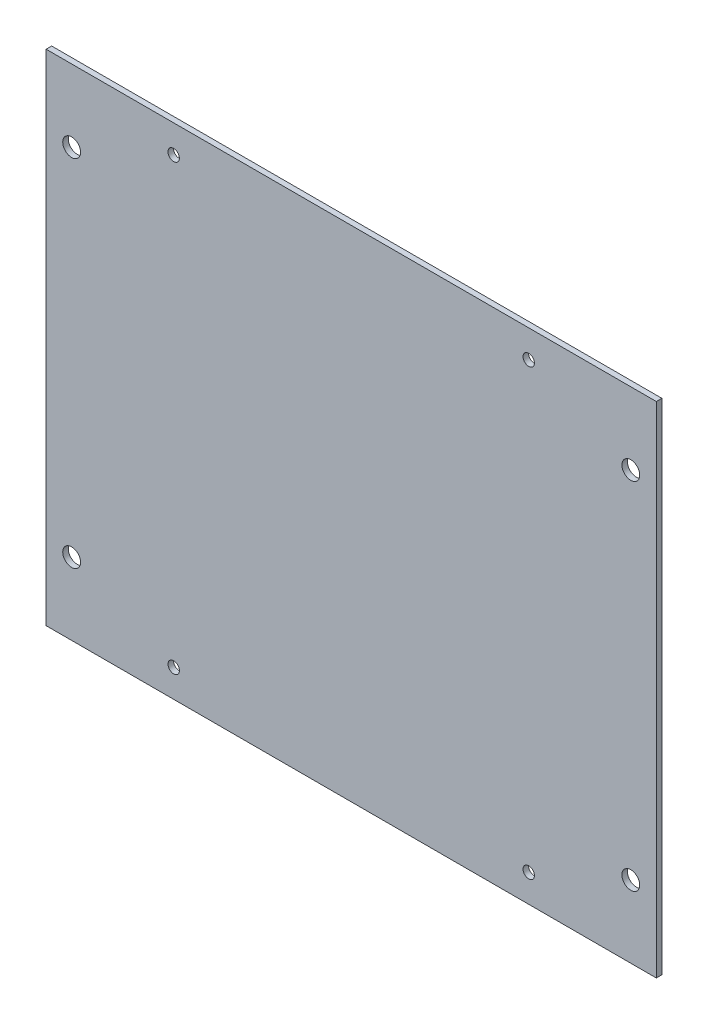
SolidWorks part; units mm, degrees
material "Perspex (TM) GS Acrylic Cast Sheet"
ref_plane "Front Plane" through (0, 0, 0) normal (0, 0, 1) x (1, 0, 0)
ref_plane "Top Plane" through (0, 0, 0) normal (0, 1, 0) x (1, 0, 0)
ref_plane "Right Plane" through (0, 0, 0) normal (1, 0, 0) x (0, 0, -1)
sketch "Sketch1" plane through (0, 0, 0) normal (0, 0, 1) x (1, 0, 0)
  line L1 (-457.2, -304.8) -> (457.2, -304.8)
  line L2 (-457.2, -304.8) -> (-457.2, 304.8)
  line L3 (-457.2, 304.8) -> (457.2, 304.8)
  line L4 (457.2, -304.8) -> (457.2, 304.8)
  line L5 (0, 304.8) -> (0, -304.8) construction
  line L6 (-457.2, 0) -> (457.2, 0) construction
  point P0 (0, 0)
  point P4 (-320.04, 0)
  point P5 (320.04, 0)
  point P6 (0, 213.36)
  point P7 (0, -213.36)
  dimension "Length" = 914.4
  dimension "Width" = 609.6
  dimension "Break" = 137.16
  dimension "D2" = 137.16
  dimension "D1" = 91.44
  dimension "D3" = 91.44
sketch "Sketch2" plane through (0, 0, 0) normal (1, 0, 0) x (0, 0, -1)
  line L0 (-0.7938, -304.8) -> (0.7938, -304.8)
  dimension "Thickness" = 1.5875
sketch "Sketch3" plane through (0, 0, 0) normal (0, 0, 1) x (1, 0, 0)
  line L0 (-457.2, -304.8) -> (-457.2, 304.8) construction
  line L1 (-457.2, -304.8) -> (457.2, -304.8) construction
  line L2 (457.2, -304.8) -> (457.2, 304.8) construction
  line L3 (-457.2, 304.8) -> (457.2, 304.8) construction
  line L4 (-457.2, -304.8) -> (-457.2, 304.8)
  line L5 (-457.2, -304.8) -> (457.2, -304.8)
  line L6 (457.2, -304.8) -> (457.2, 304.8)
  line L7 (-457.2, 304.8) -> (457.2, 304.8)
extrude "Boss-Extrude1" add sketch "Sketch3" along normal mid plane 1.5875
sketch "Sketch4" plane through (0, 0, -0.7937) normal (0, 0, -1) x (-1, 0, 0)
  line L0 (393.2038, -83.3091) -> (218.5788, -83.3085)
  line L1 (218.5788, -83.3085) -> (218.5788, 59.5665)
  line L2 (218.5788, 59.5665) -> (393.2038, 59.5659)
  line L3 (393.2038, 59.5659) -> (393.2038, -83.3091)
extrude "Cut-Extrude1" cut sketch "Sketch4" against normal blind 2.54 flip side to cut
sketch "Sketch8" plane through (0, 0, -0.7937) normal (0, 0, -1) x (-1, 0, 0)
  line L0 (305.8913, -83.3088) -> (305.8913, 59.5662) construction
  line L1 (218.5788, -83.3085) -> (393.2038, -83.3091) construction
  line L2 (393.2038, 59.5659) -> (218.5788, 59.5665) construction
  line L3 (305.8913, -11.8713) -> (255.0913, -11.8713) construction
  line L4 (255.0913, -11.8713) -> (255.0913, -75.3713) construction
  line L5 (255.0913, -75.3713) -> (356.6913, -75.3713) construction
  line L6 (356.6913, -75.3713) -> (356.6913, 51.6287) construction
  line L7 (356.6913, 51.6287) -> (255.0913, 51.6287) construction
  line L8 (255.0913, 51.6287) -> (255.0913, -11.8713) construction
hole_wizard "#4 Clearance Hole1" positions "Sketch9" profile "Sketch10" hole size "#4" standard "ANSI Inch" end condition through all
sketch "Sketch9" plane through (0, 0, -0.7937) normal (0, 0, -1) x (-1, 0, 0)
  line L0 (356.3896, 51.6036) -> (357.0296, 51.6036) construction
  point P0 (255.0913, -75.371)
  point P3 (356.6913, -75.3713)
  point P6 (356.7096, 51.6036)
  point P10 (255.0913, 51.629)
sketch "Sketch10" plane through (-255.0913, -75.371, -0.7937) normal (1, 0, 0) x (0, 1, 0)
  line L0 (0, 0) -> (0, 1.5875)
  line L1 (0, 1.5875) -> (1.6319, 1.5875)
  line L2 (1.6319, 1.5875) -> (1.6319, 0)
  line L5 (1.6319, 0) -> (0, 0)
  line L11 (0, -6.35) -> (0, 107.95) construction
  dimension "Thru Hole Dia." = 3.2639
  dimension "Thru Hole Depth" = 1.5875
hole_wizard "#10 Clearance Hole1" positions "Sketch11" profile "Sketch12" hole size "#10" standard "ANSI Inch" end condition through all
sketch "Sketch11" plane through (0, 0, -0.7937) normal (0, 0, -1) x (-1, 0, 0)
  point P0 (225.8813, -62.6713)
  point P3 (225.8813, 38.9287)
  point P6 (385.9013, 38.9287)
  point P9 (385.9013, -62.6713)
sketch "Sketch12" plane through (-225.8813, -62.6713, -0.7937) normal (1, 0, 0) x (0, 1, 0)
  line L0 (0, 0) -> (0, 1.5875)
  line L1 (0, 1.5875) -> (2.5527, 1.5875)
  line L2 (2.5527, 1.5875) -> (2.5527, 0)
  line L5 (2.5527, 0) -> (0, 0)
  line L11 (0, -6.35) -> (0, 107.95) construction
  dimension "Thru Hole Dia." = 5.1054
  dimension "Thru Hole Depth" = 1.5875
equation "\"D1@Boss-Extrude1\"=\"thickness@sketch2\""
equation "\"Break@Sketch1\" = \"Length@Sketch1\" * 0.15"
equation "\"D2@Sketch1\" = \"Break@Sketch1\""
equation "\"D1@Sketch1\"=\"Width@Sketch1\"*0.15"
equation "\"D3@Sketch1\"=\"D1@Sketch1\""
